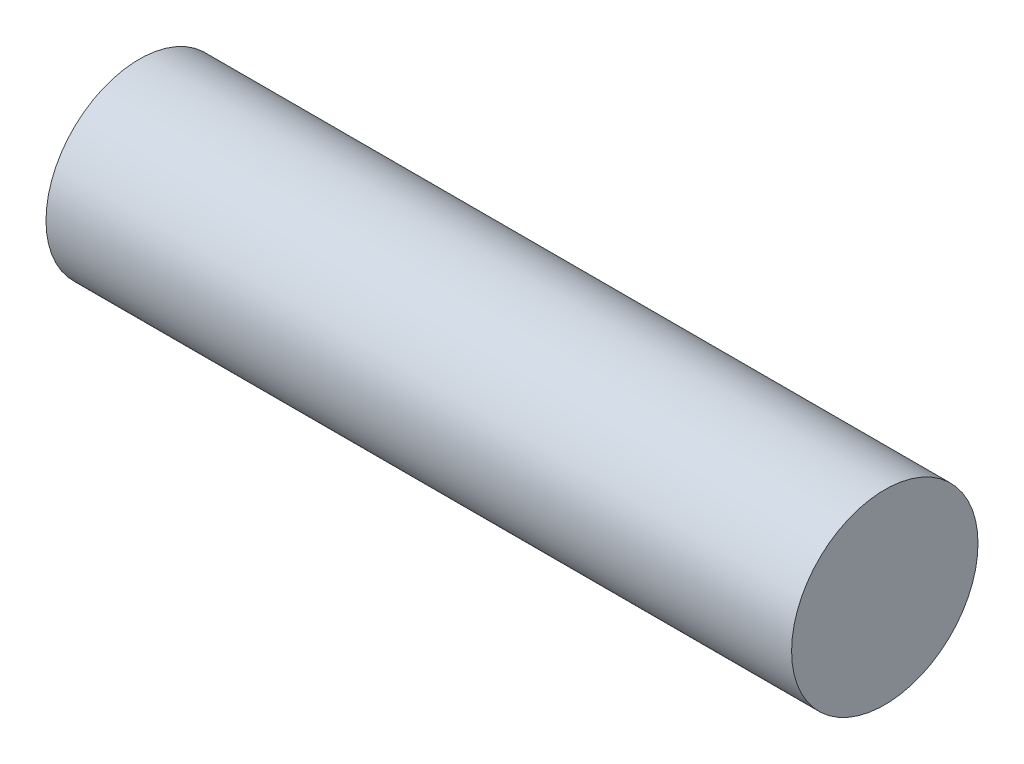
SolidWorks part; units mm, degrees
ref_plane "Front" through (0, 0, 0) normal (0, 0, 1) x (1, 0, 0)
ref_plane "Top" through (0, 0, 0) normal (0, 1, 0) x (1, 0, 0)
ref_plane "Right" through (0, 0, 0) normal (1, 0, 0) x (0, 0, -1)
sketch "Sketch1" plane through (0, 0, 0) normal (1, 0, 0) x (0, 0, -1)
  circle A0 centre (0, 0) radius 6.35
  dimension "D1" = 12.7
extrude "Boss-Extrude1" add sketch "Sketch1" along normal mid plane 50.8
